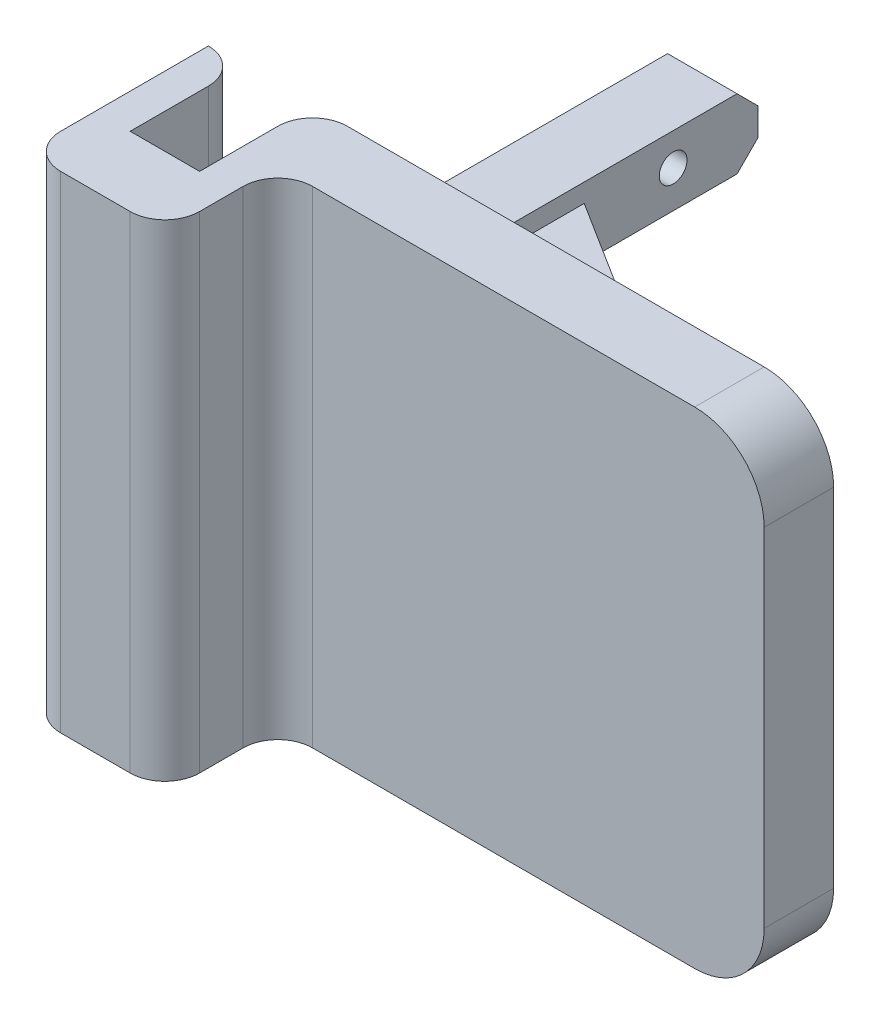
SolidWorks part; units mm, degrees
ref_plane "Plan de face" through (0, 0, 0) normal (0, 0, 1) x (1, 0, 0)
ref_plane "Plan de dessus" through (0, 0, 0) normal (0, 1, 0) x (1, 0, 0)
ref_plane "Plan de droite" through (0, 0, 0) normal (1, 0, 0) x (0, 0, -1)
sketch "Esquisse1" plane through (0, 0, 0) normal (0, 0, 1) x (1, 0, 0)
  line L1 (-17.5, 17.5) -> (17.5, 17.5)
  line L2 (-17.5, 17.5) -> (-17.5, -17.5)
  line L3 (-17.5, -17.5) -> (17.5, -17.5)
  line L4 (17.5, 17.5) -> (17.5, -17.5)
  line L5 (-17.5, 17.5) -> (17.5, -17.5) construction
  line L6 (-17.5, -17.5) -> (17.5, 17.5) construction
  point P0 (0, 0)
  dimension "D1" = 35
  dimension "D2" = 35
extrude "Boss.-Extru.1" add sketch "Esquisse1" along normal blind 5
sketch "Esquisse2" plane through (0, 0, 0) normal (0, 0, -1) x (-1, 0, 0)
  line L0 (25, 15) -> (25, -15)
  line L1 (27.5, 17.5) -> (25, 17.5)
  line L2 (27.5, 17.5) -> (27.5, -17.5)
  line L3 (27.5, -17.5) -> (25, -17.5)
  line L4 (17.5, 17.5) -> (17.5, -17.5)
  line L5 (27.5, 17.5) -> (17.5, -17.5) construction
  line L6 (27.5, -17.5) -> (17.5, 17.5) construction
  line L8 (20, 15) -> (20, -15)
  line L10 (20, -15) -> (20, -17.5)
  line L11 (25, -15) -> (25, -17.5)
  line L12 (20, -17.5) -> (17.5, -17.5)
  line L13 (27.5, -17.5) -> (17.5, -17.5) construction
  line L14 (25, -15) -> (20, -15) construction
  line L15 (25, 15) -> (20, 15) construction
  line L16 (20, 15) -> (20, 17.5)
  line L17 (25, 15) -> (25, 17.5)
  line L18 (20, 17.5) -> (17.5, 17.5)
  line L19 (27.5, 17.5) -> (17.5, 17.5) construction
  point P0 (22.5, 0)
  dimension "D1" = 10
  dimension "D2" = 2.5
extrude "Boss.-Extru.2" add sketch "Esquisse2" against normal blind 13.13
sketch "Esquisse3" plane through (-20, 0, 0) normal (-1, 0, 0) x (0, 0, 1)
  line L0 (8.13, 17.5) -> (8.13, -17.5)
  line L4 (0, 17.5) -> (0, -17.5)
  line L5 (0, -17.5) -> (13.13, -17.5)
  line L6 (13.13, -17.5) -> (13.13, 17.5)
  line L7 (13.13, 17.5) -> (0, 17.5)
  line L9 (8.13, -17.5) -> (13.13, -17.5)
  line L10 (13.13, -17.5) -> (13.13, 17.5)
  line L11 (13.13, 17.5) -> (8.13, 17.5)
  dimension "D2" = 5
  dimension "D1" = 0
extrude "Boss.-Extru.3" add sketch "Esquisse3" along normal blind 5
sketch "Esquisse4" plane through (-27.5, 0, 0) normal (-1, 0, 0) x (0, 0, 1)
  line L0 (0, -17.5) -> (-20.5, -17.5)
  line L1 (0, -17.5) -> (0, 17.5) construction
  line L2 (13.13, -17.5) -> (0, -17.5) construction
  line L3 (-20.5, -17.5) -> (-20.5, -12.85)
  line L4 (-20.5, -12.85) -> (0, -12.85)
  line L5 (0, -12.85) -> (0, -17.5)
  dimension "D1" = 20.5
  dimension "D2" = 4.65
extrude "Boss.-Extru.4" add sketch "Esquisse4" along normal blind 5 from offset 19.05 offset against normal yes
sketch "Esquisse5" plane through (0, -12.85, 0) normal (0, 1, 0) x (1, 0, 0)
  line L4 (-8.45, 0) -> (-8.45, 20.5)
  line L5 (-8.45, 20.5) -> (-13.45, 20.5)
  line L6 (-13.45, 20.5) -> (-13.45, 0)
  line L7 (-13.45, 0) -> (-8.45, 0)
  line L8 (-8.45, 0) -> (-8.45, 20.5)
  line L9 (-8.45, 20.5) -> (-13.45, 20.5)
  line L10 (-13.45, 20.5) -> (-13.45, 0)
  line L11 (-13.45, 0) -> (-8.45, 0)
  dimension "D1" = 0
extrude "Boss.-Extru.5" add sketch "Esquisse5" against normal blind 5 from offset 27.4
sketch "Esquisse6" plane through (0, -17.5, 0) normal (0, -1, 0) x (1, 0, 0)
  line L0 (-8.45, -8) -> (4.2386, 0)
  line L1 (-8.45, -20.5) -> (-8.45, 0) construction
  line L2 (-8.45, 0) -> (17.5, 0) construction
  line L3 (4.2386, 0) -> (-8.45, 0)
  line L4 (-8.45, 0) -> (-8.45, -8)
  dimension "D1" = 8
  dimension "D2" = 15
extrude "Boss.-Extru.6" add sketch "Esquisse6" against normal blind 2.325 from offset 1.1625 offset against normal yes
sketch "Esquisse7" plane through (0, -14.0125, 0) normal (0, 1, 0) x (1, 0, 0)
  line L3 (-8.45, 8) -> (-8.45, 0)
  line L4 (-8.45, 0) -> (4.2386, 0)
  line L5 (4.2386, 0) -> (-8.45, 8)
  line L6 (-8.45, 8) -> (-8.45, 0)
  line L7 (-8.45, 0) -> (4.2386, 0)
  line L8 (4.2386, 0) -> (-8.45, 8)
  dimension "D1" = 0
extrude "Boss.-Extru.7" add sketch "Esquisse7" against normal blind 2.325 from offset 27.225
fillet "Congé3" radius 5 1 edges at (-2.1057, -16.3375, 0)
fillet "Congé4" radius 1.3 1 edges at (-2.1057, 13.2125, 0)
fillet "Congé5" radius 5 2 edges at (17.5, 17.5, 2.5) (17.5, -17.5, 2.5)
sketch "Esquisse8" plane through (-8.45, 0, 0) normal (1, 0, 0) x (0, 0, -1)
  circle A0 centre (14.4, 12.225) radius 1
  circle A1 centre (14.4, -15.175) radius 1
extrude "Enlèv. mat.-Extru.1" cut sketch "Esquisse8" against normal through all
chamfer "Chanfrein1" distance 1.5 angle 45 4 edges at (-10.95, 14.55, -20.5) (-10.95, 9.55, -20.5) (-10.95, -12.85, -20.5) (-10.95, -17.5, -20.5)
fillet "Congé6" radius 5 2 edges at (-10.95, 9.55, 0) (-10.95, -12.85, 0)
fillet "Congé7" radius 2.5 2 edges at (-27.5, 0, 13.13) (-17.5, 0, 13.13)
fillet "Congé8" radius 2.5 1 edges at (-17.5, 0, 5)
fillet "Congé9" radius 2.5 2 edges at (-25, 0, 0) (-20, 0, 0)
sketch "Esquisse9" plane through (-25, 0, 0) normal (1, 0, 0) x (0, 0, -1)
  line L0 (-5.315, 17.5) -> (-5.315, -17.5) construction
  line L1 (-2.5, 0) -> (-8.13, 0) construction
  line L4 (-8.13, -17.5) -> (-2.5, -17.5)
  line L5 (-2.5, -17.5) -> (-2.5, 17.5)
  line L6 (-2.5, 17.5) -> (-8.13, 17.5)
  line L7 (-8.13, 17.5) -> (-8.13, -17.5)
  line L8 (-8.13, -17.5) -> (-2.5, -17.5)
  line L9 (-2.5, -17.5) -> (-2.5, 17.5) construction
  line L10 (-2.5, 17.5) -> (-8.13, 17.5)
  line L11 (-8.13, 17.5) -> (-8.13, -17.5)
  circle A0 centre (-5.315, 12) radius 1.5
  circle A1 centre (-5.315, -12) radius 1.5
  dimension "D3" = 3
  dimension "D2" = 12
  dimension "D1" = 0
extrude "Enlèv. mat.-Extru.2" cut sketch "Esquisse9" against normal through all contours A1 | A0 region at (-25, 12, 5.315) region at (-25, -12, 5.315)
